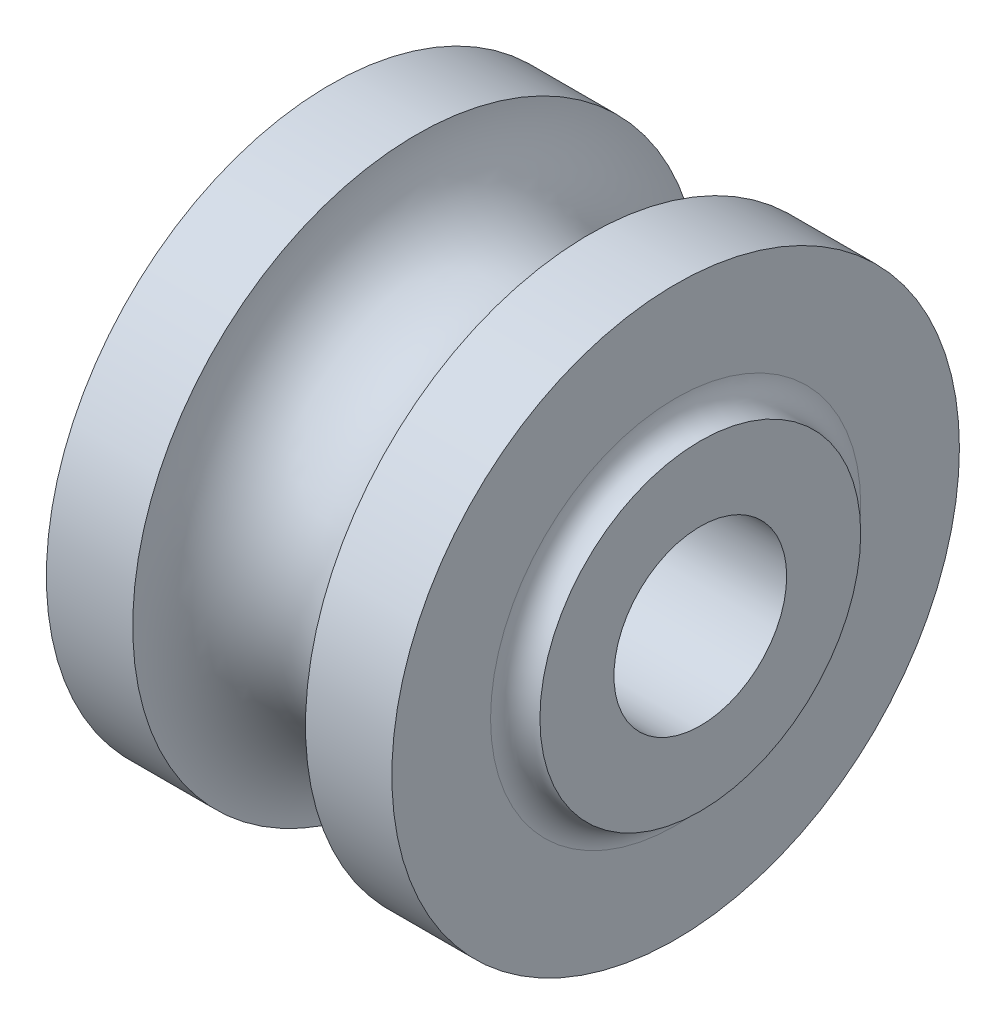
SolidWorks part; units mm, degrees
ref_plane "Front Plane" through (0, 0, 0) normal (0, 0, 1) x (1, 0, 0)
ref_plane "Top Plane" through (0, 0, 0) normal (0, 1, 0) x (1, 0, 0)
ref_plane "Right Plane" through (0, 0, 0) normal (1, 0, 0) x (0, 0, -1)
sketch "Sketch1" plane through (0, 0, 0) normal (0, 0, 1) x (1, 0, 0)
  line L1 (-14, 23) -> (-7, 23)
  line L2 (14, 23) -> (14, 13)
  line L3 (14, 13) -> (16, 13)
  line L4 (16, 13) -> (16, 0)
  line L6 (0, -55) -> (0, 55) construction
  line L7 (-16, 13) -> (-16, 0)
  line L8 (-14, 13) -> (-16, 13)
  line L9 (-14, 23) -> (-14, 13)
  line L10 (-16, 0) -> (16, 0)
  line L11 (7, 23) -> (14, 23)
  line L12 (0, 0) -> (-24.4691, 0) construction
  arc A0 (-7, 23) -> (7, 23) centre (0, 23) ccw
  dimension "D3" = 7
  dimension "D1" = 13
  dimension "D2" = 2
  dimension "D4" = 32
  dimension "D5" = 23
revolve "Revolve1" add sketch "Sketch1" angle 360 about L12
fillet "Fillet1" radius 2 2 edges at (-14, 0, -13) (14, 0, -13)
hole_wizard "Hole1" positions "Sketch2" profile "Sketch3" legacy end condition through all
sketch "Sketch2" plane through (16, 0, 0) normal (1, 0, 0) x (0, 0, -1)
  point P0 (0, 0)
sketch "Sketch3" plane through (16, 0, 0) normal (0, 1, 0) x (0, 0, -1)
  line L0 (0, 0) -> (0, 32)
  line L1 (0, 32) -> (7, 32)
  line L2 (7, 32) -> (7, 0)
  line L3 (7, 0) -> (0, 0)
  line L4 (0, 110) -> (0, -10) construction
  dimension "Diameter" = 14
  dimension "Depth" = 32
